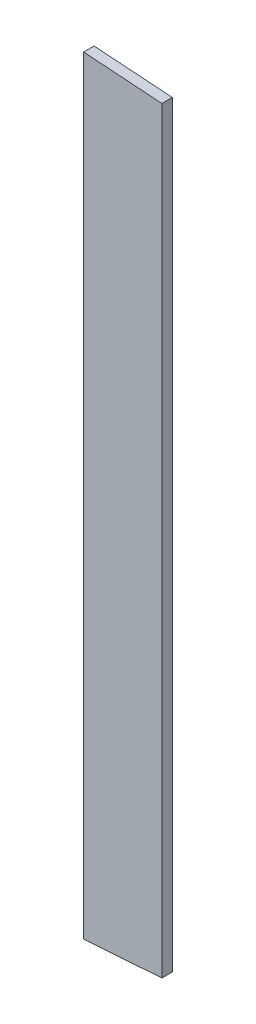
SolidWorks part; units mm, degrees
ref_plane "Front Plane" through (0, 0, 0) normal (0, 0, 1) x (1, 0, 0)
ref_plane "Top Plane" through (0, 0, 0) normal (0, 1, 0) x (1, 0, 0)
ref_plane "Right Plane" through (0, 0, 0) normal (1, 0, 0) x (0, 0, -1)
sketch "Sketch1" plane through (0, 0, 3768.95) normal (0, 0, 1) x (1, 0, 0)
  line L0 (-49.7697, 346.1083) -> (-64.7697, 345.0594)
  line L1 (-140.9262, 339.734) -> (58.5866, 353.6853) construction
  line L2 (-64.7697, 345.0594) -> (-64.7697, 492.4158)
  line L3 (58.5866, 483.7899) -> (-140.9262, 497.7412) construction
  line L4 (-64.7697, 492.4158) -> (-49.7697, 491.3669)
  line L5 (-49.7697, 491.3669) -> (-49.7697, 346.1083)
  dimension "D1" = 15
extrude "Boss-Extrude1" add sketch "Sketch1" along normal blind 2
ref_plane "Plane1" through (-57.2697, 0, 0) normal (1, 0, 0) x (0, 0, -1)
